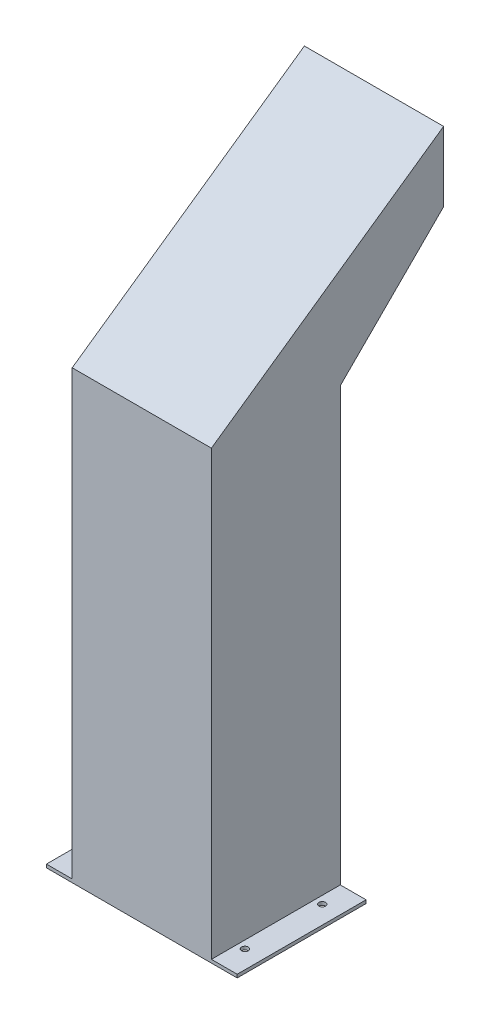
SolidWorks part; units mm, degrees
ref_plane "Front Plane" through (0, 0, 0) normal (0, 0, 1) x (1, 0, 0)
ref_plane "Top Plane" through (0, 0, 0) normal (0, 1, 0) x (1, 0, 0)
ref_plane "Right Plane" through (0, 0, 0) normal (1, 0, 0) x (0, 0, -1)
sketch "Sketch2" plane through (0, 0, 0) normal (0, 0, 1) x (1, 0, 0)
  line L0 (-577.7442, 0) -> (577.7442, 0) construction
  line L1 (0, -368.7209) -> (0, 368.7209) construction
  line L2 (-135, 0) -> (135, 0)
  line L3 (135, 6.35) -> (135, 845)
  line L4 (135, 845) -> (-135, 845)
  line L5 (-135, 6.35) -> (-135, 845)
  line L6 (128.65, 838.65) -> (-128.65, 838.65) construction
  line L7 (-128.65, 6.35) -> (-128.65, 838.65) construction
  line L8 (-128.65, 6.35) -> (128.65, 6.35) construction
  line L9 (128.65, 6.35) -> (128.65, 838.65) construction
  line L10 (135, 6.35) -> (185, 6.35)
  line L11 (185, 6.35) -> (185, 0)
  line L12 (185, 0) -> (135, 0)
  line L13 (-185, 6.35) -> (-185, 0)
  line L14 (-185, 0) -> (-135, 0)
  line L15 (-135, 6.35) -> (-185, 6.35)
  line L17 (135, 0) -> (135, 845) construction
  line L18 (-135, 0) -> (-135, 845) construction
  point P4 (0, 0)
  point P8 (0, 0)
  point P13 (0, 0)
  point P14 (0, 845)
  dimension "D1" = 135
  dimension "D2" = 845
  dimension "D3" = 6.35
  dimension "D4" = 50
extrude "Boss-Extrude1" add sketch "Sketch2" along normal mid plane 250
sketch "Sketch3" plane through (0, 845, 0) normal (0, 1, 0) x (1, 0, 0)
  line L0 (-135, 125) -> (135, 125) construction
  line L1 (135, 125) -> (135, -125) construction
  line L2 (135, -125) -> (-135, -125) construction
  line L3 (-135, -125) -> (-135, 125) construction
  line L4 (-128.65, 118.65) -> (128.65, 118.65)
  line L5 (128.65, 118.65) -> (128.65, -118.65)
  line L6 (128.65, -118.65) -> (-128.65, -118.65)
  line L7 (-128.65, -118.65) -> (-128.65, 118.65)
  dimension "D1" = 6.35
extrude "Cut-Extrude1" cut sketch "Sketch3" against normal blind 1000
sketch "Sketch5" plane through (0, 0, 0) normal (1, 0, 0) x (0, 0, -1)
  line L0 (-275.3165, 845) -> (275.3165, 845) construction
  line L2 (0, 516.6009) -> (0, 1173.3991) construction
  line L3 (-125, 865) -> (325.3115, 1180.3115)
  line L4 (-125, 845) -> (125, 845)
  line L5 (-125, 845) -> (-125, 865)
  line L8 (325.3115, 1180.3115) -> (325.3115, 1045.3115)
  line L9 (325.3115, 1045.3115) -> (125, 845)
  point P3 (0, 845)
  point P7 (0, 845)
  point P12 (127, 845)
  point P15 (0, 0)
  dimension "D1" = 20
  dimension "D2" = 135
  dimension "D3" = 125
  dimension "D4" = 45
extrude "Boss-Extrude2" add sketch "Sketch5" along normal mid plane 270
shell "Shell1" thickness 10 removed face at (0, 1112.8115, -325.3115)
sketch "Sketch6" plane through (0, 0, 0) normal (0, -1, 0) x (1, 0, 0)
  line L0 (-413.1171, 0) -> (413.1171, 0) construction
  line L1 (0, -401.3002) -> (0, 401.3002) construction
  line L2 (125, -198.295) -> (125, 198.295) construction
  line L3 (150, -204.6246) -> (150, 204.6246) construction
  line L4 (-276.5763, 75) -> (276.5763, 75) construction
  circle A1 centre (150, 75) radius 6.5
  circle A2 centre (150, -75) radius 6.5
  circle A3 centre (-150, 75) radius 6.5
  circle A4 centre (-150, -75) radius 6.5
  point P4 (0, 0)
  point P8 (0, 0)
  point P11 (125, 0)
  point P14 (150, 0)
  point P17 (0, 75)
  dimension "D4" = 13
  dimension "D1" = 125
  dimension "D2" = 150
  dimension "D3" = 75
extrude "Cut-Extrude2" cut sketch "Sketch6" against normal blind 30
